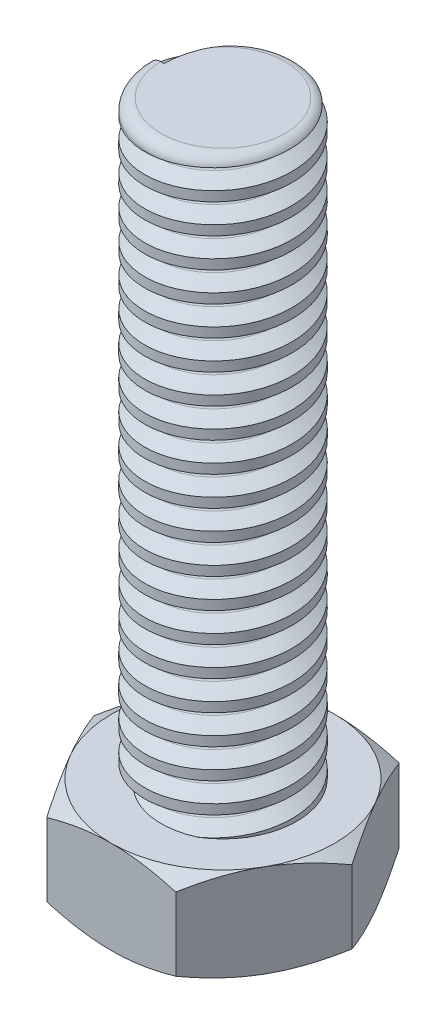
SolidWorks part; units mm, degrees
material "1.0420 (G200)"
ref_plane "Plano frontal" through (0, 0, 0) normal (0, 0, 1) x (1, 0, 0)
ref_plane "Plano superior" through (0, 0, 0) normal (0, 1, 0) x (1, 0, 0)
ref_plane "Plano direito" through (0, 0, 0) normal (1, 0, 0) x (0, 0, -1)
sketch "Esboço2" plane through (0, 0, 0) normal (0, 1, 0) x (1, 0, 0)
  line L1 (5.555, 0) -> (2.7775, 4.8108)
  line L2 (2.7775, 4.8108) -> (-2.7775, 4.8108)
  line L3 (-2.7775, 4.8108) -> (-5.555, 0)
  line L4 (-5.555, 0) -> (-2.7775, -4.8108)
  line L5 (-2.7775, -4.8108) -> (2.7775, -4.8108)
  line L6 (2.7775, -4.8108) -> (5.555, 0)
  circle A0 centre (0, 0) radius 4.8108 construction
  dimension "D1" = 11.11
extrude "Ressalto-extrusão1" add sketch "Esboço2" along normal blind 4
sketch "Esboço3" plane through (0, 4, 0) normal (0, 1, 0) x (1, 0, 0)
  circle A0 centre (0, 0) radius 3.175
  dimension "D1" = 6.35
extrude "Ressalto-extrusão2" add sketch "Esboço3" along normal blind 25.4 contours A0
sketch "Esboço8" plane through (0, 29.4, 0) normal (0, 1, 0) x (1, 0, 0)
  circle A0 centre (0, 0) radius 3.175
  dimension "D1" = 6.35
curve "Hélice/Espiral1" pitch 1.27 height 25.4 turns 20
fillet "Filete1" radius 0.5 1 edges at (0, 29.4, 3.175)
sketch "Esboço10" plane through (0, 0, 0) normal (0, 0, 1) x (1, 0, 0)
  line L1 (-2.586, 29.4866) -> (-3.5445, 30.04)
  line L2 (-3.5445, 30.04) -> (-3.5445, 28.76)
  line L3 (-3.5445, 28.76) -> (-2.586, 29.3134)
  circle A0 centre (-3.175, 29.4) radius 0.3695 construction
  arc A1 (-2.586, 29.4866) -> (-2.586, 29.3134) centre (-2.636, 29.4) cw
  point P11 (-2.436, 29.4)
  dimension "D2" = 0.1
  dimension "D1" = 1.28
sweep "Varredura de corte3" cut profiles "Esboço10" path "Hélice/Espiral1"
sketch "Esboço11" plane through (0, 0, 0) normal (0, -1, 0) x (1, 0, 0)
  circle A0 centre (0, 0) radius 4.8108
  dimension "D1" = 9.6215
extrude "Corte-extrusão1" cut sketch "Esboço11" against normal blind 10 draft 60 flip side to cut
ref_plane "Plano2" through (0, 2, 0) normal (0, 1, 0) x (1, 0, 0)
mirror "Espelhar1" about plane through (0, 2, 0) normal (0, 1, 0) of "Corte-extrusão1"
